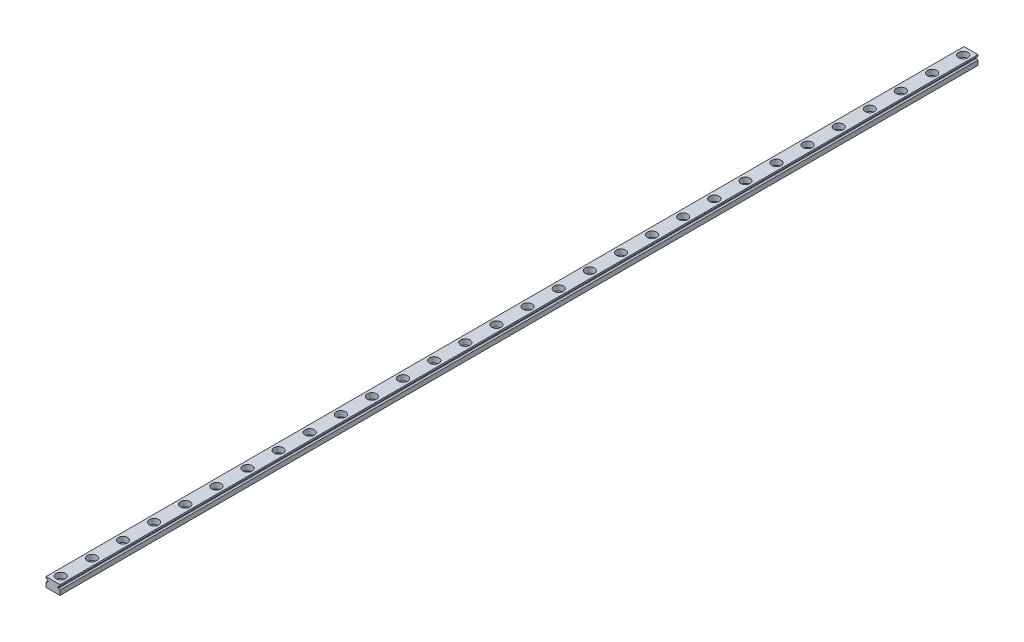
SolidWorks part; units mm, degrees
ref_plane "Front Plane" through (0, 0, 0) normal (0, 0, 1) x (1, 0, 0)
ref_plane "Top Plane" through (0, 0, 0) normal (0, 1, 0) x (1, 0, 0)
ref_plane "Right Plane" through (0, 0, 0) normal (1, 0, 0) x (0, 0, -1)
sketch "Sketch1" plane through (0, 0, 0) normal (0, 0, 1) x (1, 0, 0)
  line L0 (0, 0) -> (0, 5.7299) construction
  line L1 (-4.5, -3) -> (4.5, -3)
  line L2 (-4.5, -3) -> (-4.5, 0)
  line L3 (-4.5, 3) -> (4.5, 3)
  line L4 (4.5, -3) -> (4.5, 0)
  line L5 (-4.5, -3) -> (4.5, 3) construction
  line L6 (-4.5, 3) -> (4.5, -3) construction
  line L7 (-4.5, 2) -> (-4.5, 3)
  line L8 (-3.564, 0.648) -> (-3.2351, 0.648)
  line L9 (3.564, 0.648) -> (3.2351, 0.648)
  line L10 (-3.564, 1.352) -> (-3.2351, 1.352)
  line L11 (-3.2351, 0.648) -> (-3.2351, 1.352)
  line L12 (3.2351, 0.648) -> (3.2351, 1.352)
  line L13 (3.564, 1.352) -> (3.2351, 1.352)
  line L14 (4.5, 2) -> (4.5, 3)
  arc A0 (-3.564, 1.352) -> (-4.5, 2) centre (-4.5, 1) ccw
  arc A1 (-4.5, 0) -> (-3.564, 0.648) centre (-4.5, 1) ccw
  arc A2 (4.5, 0) -> (3.564, 0.648) centre (4.5, 1) cw
  arc A3 (3.564, 1.352) -> (4.5, 2) centre (4.5, 1) cw
  point P0 (0, 0)
  point P22 (0, 0)
  dimension "D3" = 1
  dimension "D1" = 9
  dimension "D2" = 6
  dimension "D4" = 2
extrude "Extrude1" add sketch "Sketch1" along normal blind 590
sketch "Sketch2" plane through (0, 3, 0) normal (0, 1, 0) x (1, 0, 0)
  line L0 (4.5, 0) -> (-4.5, 0) construction
  circle A0 centre (0, -5) radius 1.75
  circle A1 centre (0, -5) radius 3
  dimension "D1" = 3.5
  dimension "D2" = 6
  dimension "D3" = 5
extrude "Extrude2" cut sketch "Sketch2" against normal blind 3.5 contours A1
extrude "Extrude3" cut sketch "Sketch" against normal through all contours A0
sketch "Sketch" plane through (0, 3, 0) normal (0, 1, 0) x (1, 0, 0) same geometry as "Sketch2"
pattern_linear "LPattern1" count 30 spacing 20 along (0, 0, 1) of "Extrude2", "Extrude3"
